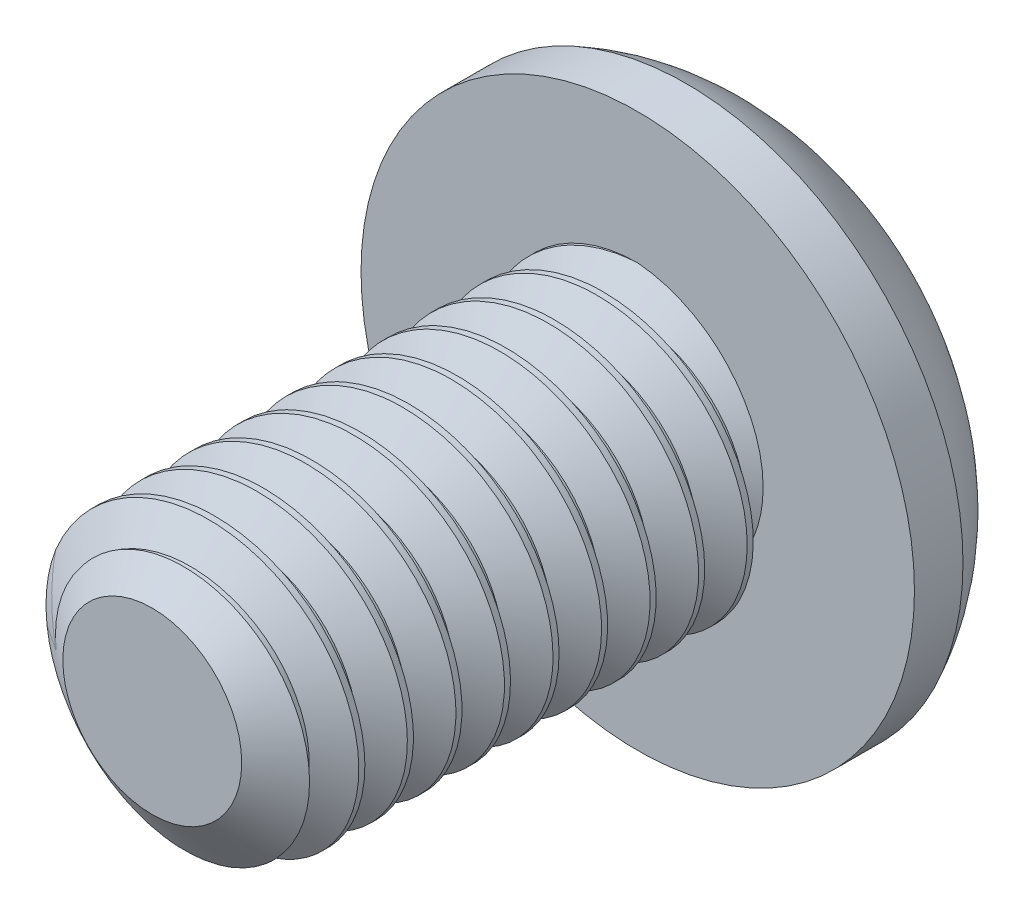
SolidWorks part; units mm, degrees
material "AISI 316 Stainless Steel Sheet (SS)"
ref_plane "Front Plane" through (0, 0, 0) normal (0, 0, 1) x (1, 0, 0)
ref_plane "Top Plane" through (0, 0, 0) normal (0, 1, 0) x (1, 0, 0)
ref_plane "Right Plane" through (0, 0, 0) normal (1, 0, 0) x (0, 0, -1)
sketch "Sketch1" plane through (0, 0, 0) normal (0, 0, 1) x (1, 0, 0)
  circle A0 centre (0, 0) radius 1.5
  dimension "OD" = 3
extrude "Extrude1" add sketch "Sketch1" against normal blind 5
sketch "Sketch2" plane through (0, 0, 0) normal (0, 0, 1) x (1, 0, 0)
  circle A0 centre (0, 0) radius 1.5 construction
  circle A1 centre (0, 0) radius 1.5
curve "Helix/Spiral1" pitch 0.5 height 5.5 radius 1.5 centre (0, 0, 0) axis (0, 0, -1) start towards (0, 1, 0) parameters "pitch"=0.5
sketch "Sketch3" plane through (0, 0, 0) normal (1, 0, 0) x (0, 0, -1)
  line L0 (-0.4375, 1.5) -> (-0.25, 1.1752)
  line L1 (-0.25, 1.1752) -> (-0.1875, 1.1752)
  line L2 (-0.1875, 1.1752) -> (0, 1.5)
  line L3 (-0.4375, 1.5) -> (0, 1.5)
  line L4 (-0.2187, 1.5) -> (-0.2187, 1.1752) construction
  line L5 (-0.3437, 1.3376) -> (-0.0937, 1.3376) construction
  line L6 (0, 1.5) -> (0, -1.5) construction
  dimension "D1" = 0.0625
  dimension "D2" = 0.25
  dimension "D3" = 60
sweep "Cut-Sweep1" cut profiles "Sketch3" path "Helix/Spiral1"
sketch "Sketch4" plane through (0, 0, 0) normal (1, 0, 0) x (0, 0, -1)
  line L0 (0.4053, 1.5) -> (0, 0.9212)
  line L1 (0, 0.9212) -> (0, 1.5)
  line L2 (0.4053, 1.5) -> (0, 1.5)
  line L3 (-0.4375, 1.5) -> (0, 1.5) construction
  line L4 (0, 0) -> (7.0209, 0) construction
  dimension "D1" = 55
  dimension "D2" = 0.254
revolve "Cut-Revolve1" cut sketch "Sketch4" angle 360 about L4
sketch "Sketch5" plane through (0, 0, 0) normal (1, 0, 0) x (0, 0, -1)
  line L0 (5, -1.1822) -> (5, 1.0703) construction
  line L1 (5, 1.627) -> (28.1202, 1.627)
  line L2 (5, 1.627) -> (5, 0)
  line L3 (5, 0) -> (28, 0)
  line L4 (28, 1.2968) -> (28, 0)
  line L5 (28.1202, 1.627) -> (28, 1.2968)
  line L6 (0, 0) -> (9.9695, 0) construction
  point P3 (28, 1.627)
  point P10 (28, 1.627)
  dimension "D1" = 0.3302
  dimension "Thread min" = 28
  dimension "D2" = 0.127
  dimension "D3" = 20
revolve "partially thread" [suppressed] add sketch "Sketch5" angle 360 about L6
sketch "Sketch6" plane through (0, 0, -5) normal (0, 0, -1) x (-1, 0, 0)
  circle A0 centre (0, 0) radius 2.85
  dimension "head dia" = 5.7
extrude "Extrude2" add sketch "Sketch6" along normal blind 1.65
sketch "Sketch10" plane through (0, 0, 0) normal (1, 0, 0) x (0, 0, -1)
  line L0 (6.65, -2.85) -> (6.65, 2.85) construction
  line L1 (0, 0) -> (15.9584, 0) construction
  line L2 (6.65, 2.85) -> (5, 2.85) construction
  line L3 (5, 2.85) -> (5, -2.85) construction
  line L4 (5.5, 2.85) -> (5.5, 3.35)
  line L5 (5.5, 3.35) -> (7.15, 3.35)
  line L6 (7.15, 3.35) -> (7.15, 1)
  line L7 (6.65, 1) -> (7.15, 1)
  arc A0 (6.65, 1) -> (5.5, 2.85) centre (4.587, 1) ccw
  dimension "D1" = 2
  dimension "D2" = 0.5
  dimension "D3" = 0.5
revolve "Cut-Revolve2" cut sketch "Sketch10" angle 360 about L1
ref_plane "Plane1" through (0, 0, -6.65) normal (0, 0, 1) x (1, 0, 0)
sketch "Sketch7" plane through (0, 0, -6.65) normal (0, 0, -1) x (-1, 0, 0)
  line L1 (0, 1.1547) -> (-1, 0.5774)
  line L2 (-1, 0.5774) -> (-1, -0.5774)
  line L3 (-1, -0.5774) -> (0, -1.1547)
  line L4 (0, -1.1547) -> (1, -0.5774)
  line L5 (1, -0.5774) -> (1, 0.5774)
  line L6 (1, 0.5774) -> (0, 1.1547)
  circle A0 centre (0, 0) radius 1 construction
  dimension "hex dia" = 2
extrude "Cut-Extrude1" cut sketch "Sketch7" against normal blind 1.5
sketch "Sketch8" plane through (0, 0, -6.65) normal (0, 0, 1) x (1, 0, 0)
  circle A0 centre (0, 0) radius 1.1547
extrude "Cut-Extrude2" cut sketch "Sketch8" along normal through all draft 45
sketch "Sketch9" plane through (0, 0, 0) normal (1, 0, 0) x (0, 0, -1)
  line L0 (0, 1.5) -> (0, -1.5) construction
  line L1 (2.75, 1.5) -> (2.75, -1.5) construction
  dimension "D1" = 2.75
equation "\"D3@Helix/Spiral1\" = \"screw length@Extrude1\"+\"pitch@Helix/Spiral1\""
equation "\"D1@Sketch3\" = \"pitch@Helix/Spiral1\"*.125"
equation "\"D2@Sketch3\" = \"pitch@Helix/Spiral1\"*.5"
equation "\"D1@Cut-Extrude1\" = \"hex dia@Sketch7\"*.75"
equation "\"D1@Sketch9\" = \"pitch@Helix/Spiral1\"*5.5"
equation "\"D1@Sketch10\" = \"hex dia@Sketch7\""
equation "\"D1@Plane1\" = \"head depth@Extrude2\""
